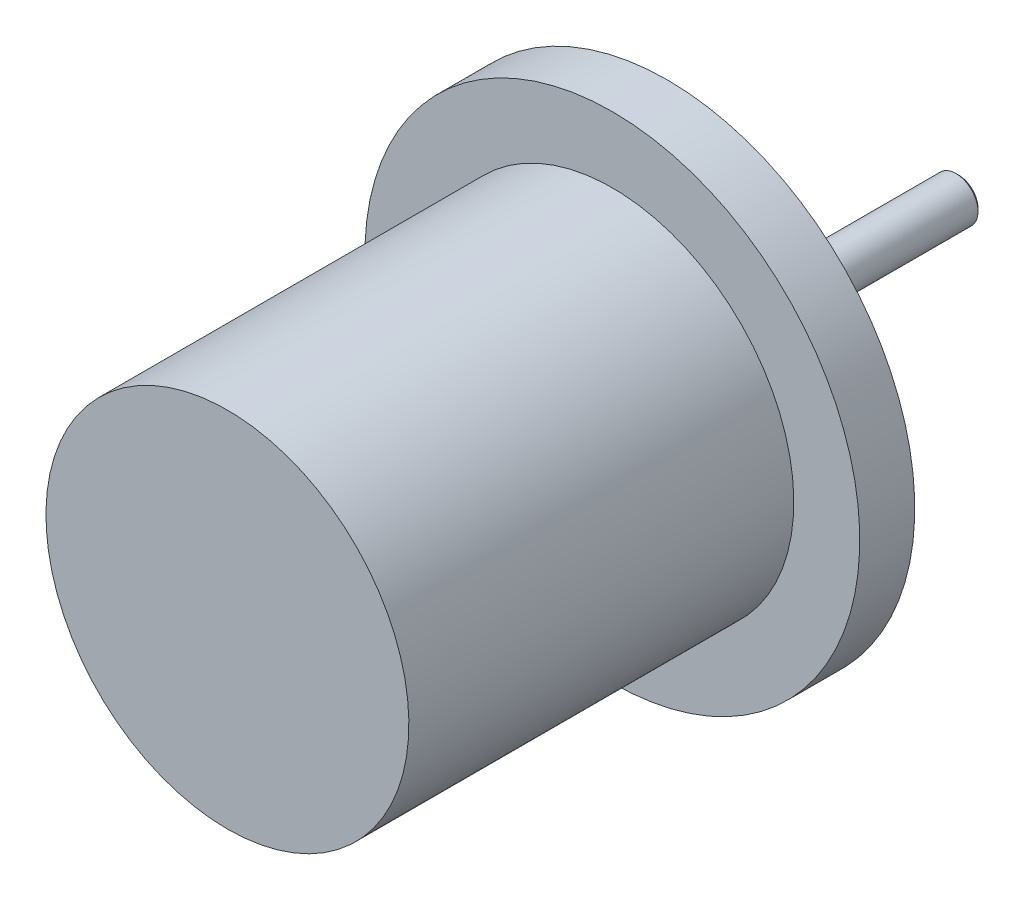
SolidWorks part; units mm, degrees
ref_plane "Front" through (0, 0, 0) normal (0, 0, 1) x (1, 0, 0)
ref_plane "Top" through (0, 0, 0) normal (0, 1, 0) x (1, 0, 0)
ref_plane "Right" through (0, 0, 0) normal (1, 0, 0) x (0, 0, -1)
sketch "Sketch1" plane through (0, 0, 0) normal (1, 0, 0) x (0, 0, -1)
  line L0 (-67.7839, 0) -> (65.2161, 0)
  line L1 (12.2161, 45) -> (12.2161, 17.5)
  line L2 (12.2161, 45) -> (2.2161, 45)
  line L3 (2.2161, 45) -> (2.2161, 33)
  line L4 (2.2161, 33) -> (-67.7839, 33)
  line L5 (-67.7839, 33) -> (-67.7839, 0)
  line L6 (15.2161, 6) -> (15.2161, 17.5)
  line L7 (15.2161, 17.5) -> (12.2161, 17.5)
  line L8 (31.2161, 6) -> (31.2161, 4)
  line L9 (31.2161, 6) -> (15.2161, 6)
  line L10 (31.2161, 4) -> (65.2161, 4)
  line L11 (65.2161, 4) -> (65.2161, 0)
  dimension "D1" = 16
  dimension "D2" = 10
  dimension "D3" = 6
  dimension "D4" = 70
  dimension "D5" = 3
  dimension "D6" = 33
  dimension "D7" = 4
  dimension "D8" = 34
  dimension "D9" = 45
revolve "Revolve1" add sketch "Sketch1" angle 360 about L0
ref_plane "Plane1" through (0, 6, 0) normal (0, 1, 0) x (1, 0, 0)
sketch "Sketch2" plane through (0, 6, 0) normal (0, 1, 0) x (1, 0, 0)
  line L2 (-2.025, 20.7323) -> (-2.025, 27.6823)
  line L4 (2.025, 27.6823) -> (2.025, 20.7323)
  arc A0 (2.025, 27.6823) -> (-2.025, 27.6823) centre (0, 27.6823) ccw
  arc A1 (-2.025, 20.7323) -> (2.025, 20.7323) centre (0, 20.7323) ccw
  dimension "D1" = 4.05
  dimension "D2" = 4.05
extrude "Cut-Extrude1" cut sketch "Sketch2" against normal blind 2.5
chamfer "Chamfer1" distance 0.5 angle 45 1 edges at (0, -6, -31.2161)
sketch "Sketch7" plane through (0, 0, -12.2161) normal (0, 0, -1) x (-1, 0, 0)
  line L0 (0, 0) -> (0, 47.9811) construction
  line L1 (0, 0) -> (33.9277, 33.9277) construction
  line L2 (0, 0) -> (47.9811, 0) construction
  line L3 (0, 0) -> (33.9277, -33.9277) construction
  line L4 (0, 0) -> (0, -47.9811) construction
  line L5 (0, 0) -> (-33.9277, -33.9277) construction
  line L6 (0, 0) -> (-47.9811, 0) construction
  line L7 (0, 0) -> (-33.9277, 33.9277) construction
  circle A0 centre (0, 0) radius 35
  circle A1 centre (0, 35) radius 3
  circle A2 centre (24.7487, 24.7487) radius 3
  circle A3 centre (35, 0) radius 3
  circle A4 centre (24.7487, -24.7487) radius 3
  circle A5 centre (0, -35) radius 3
  circle A6 centre (-24.7487, -24.7487) radius 3
  circle A7 centre (-35, 0) radius 3
  circle A8 centre (-24.7487, 24.7487) radius 3
  point P13 (0, 0)
  point P31 (0, 0)
  dimension "D1" = 70
  dimension "D3" = 6
  dimension "D2" = 8
  dimension "D4" = 8
extrude "Cut-Extrude4" cut sketch "Sketch7" against normal blind 3 contours A0 A8 | A0 A8 | A0 A7 | A0 A7 | A0 A6 | A0 A6 | A0 A5 | A0 A5 | A0 A4 | A0 A4 | A0 A3 | A0 A3 | A0 A2 | A0 A2 | A0 A1 | A0 A1 region at (-33.7039, 0, -12.2161) region at (-36.2498, 0, -12.2161) region at (-23.8322, 23.8322, -12.2161) region at (-25.6325, 25.6325, -12.2161) region at (-25.6325, -25.6325, -12.2161) region at (-23.8322, -23.8322, -12.2161) region at (0, 33.7039, -12.2161) region at (0, 36.2498, -12.2161) region at (0, -36.2498, -12.2161) region at (0, -33.7039, -12.2161) region at (23.8322, 23.8322, -12.2161) region at (25.6325, 25.6325, -12.2161) region at (25.6325, -25.6325, -12.2161) region at (23.8322, -23.8322, -12.2161) region at (33.7039, 0, -12.2161) region at (36.2498, 0, -12.2161)
cosmetic thread "Cosmetic Thread1" parameters "D2"=10
cosmetic thread "Cosmetic Thread2" parameters "D2"=10
cosmetic thread "Cosmetic Thread3" parameters "D2"=10
cosmetic thread "Cosmetic Thread4" parameters "D2"=10
cosmetic thread "Cosmetic Thread5" parameters "D2"=10
cosmetic thread "Cosmetic Thread6" parameters "D2"=10
cosmetic thread "Cosmetic Thread7" parameters "D2"=10
cosmetic thread "Cosmetic Thread8" parameters "D2"=10
sketch "Sketch8" plane through (0, 0, -65.2161) normal (0, 0, -1) x (-1, 0, 0)
  circle A0 centre (0, 0) radius 1.5
  dimension "D1" = 3
extrude "Cut-Extrude5" cut sketch "Sketch8" against normal blind 5
cosmetic thread "Cosmetic Thread11" parameters "D2"=6
chamfer "Chamfer2" distance 0.5 angle 45 1 edges at (0, -4, -65.2161)
sketch "Sketch9" plane through (0, 0, -12.2161) normal (0, 0, -1) x (-1, 0, 0)
  point P0 (-24.7487, 24.7487)
  point P1 (0, 35)
  point P3 (24.7487, 24.7487)
  point P5 (35, 0)
  point P7 (24.7487, -24.7487)
  point P9 (0, -35)
  point P11 (-24.7487, -24.7487)
  point P13 (-35, 0)
sketch "Sketch10" plane through (0, 0, -12.2161) normal (0, 0, -1) x (-1, 0, 0)
  point P0 (-35, 0)
  point P1 (35, 0)
  point P3 (0, -35)
  point P5 (0, 35)
